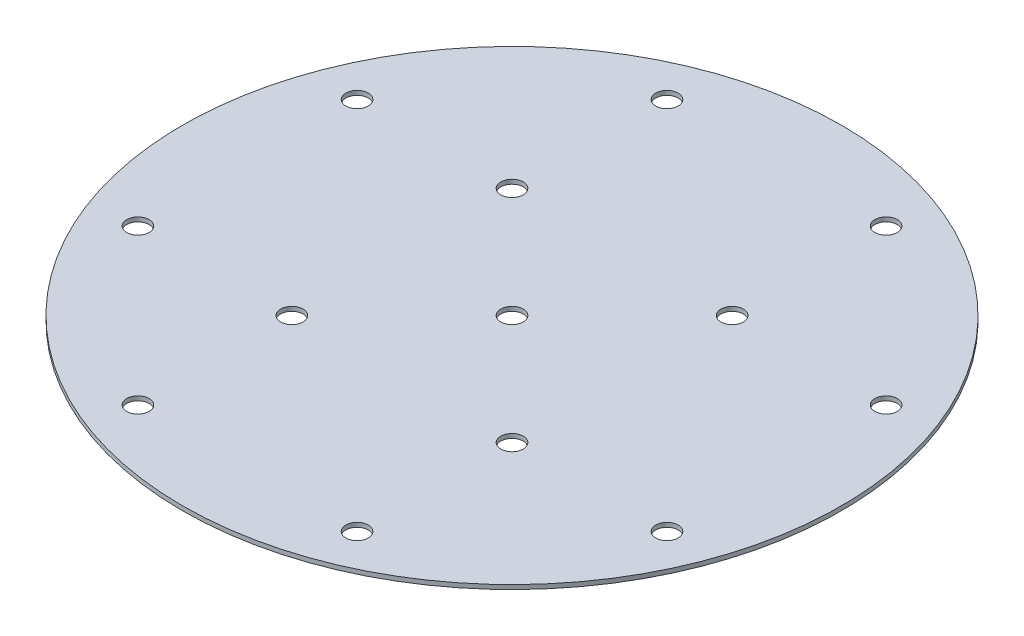
SolidWorks part; units mm, degrees
ref_plane "Front Plane" through (0, 0, 0) normal (0, 0, 1) x (1, 0, 0)
ref_plane "Top Plane" through (0, 0, 0) normal (0, 1, 0) x (1, 0, 0)
ref_plane "Right Plane" through (0, 0, 0) normal (1, 0, 0) x (0, 0, -1)
sketch "Sketch2" plane through (0, 0, 0) normal (1, 0, 0) x (0, 0, -1)
  line L0 (0, 0) -> (-76.2, 0)
  line L1 (-76.2, 0) -> (-76.2, 1)
  line L2 (-76.2, 1) -> (0, 1)
  line L5 (0, 1) -> (0, 0)
  dimension "D1" = 76.2
  dimension "D2" = 1
ref_axis "Axis1" through (0, -0.05, 0) along (0, 1, 0)
revolve "Revolve1" add sketch "Sketch2" angle 360 about axis through (0, -0.05, 0) along (0, 1, 0)
hole_wizard "#6 (0.204) Diameter Hole1" positions "Sketch6" profile "Sketch7" hole size "#6" standard "ANSI Inch" end condition through all
sketch "Sketch6" plane through (0, 1, 0) normal (0, 1, 0) x (1, 0, 0)
  line L0 (0, 0) -> (-53.438, 129.0108) construction
  line L2 (0, 0) -> (0, 109.0908) construction
  line L3 (0, 0) -> (-70.3996, 29.1605) construction
  line L4 (0, 0) -> (-47.7784, 47.7784) construction
  circle A0 centre (0, 0) radius 76.2 construction
  point P0 (-25.3336, 61.1608)
  point P11 (264.7437, 73.7878)
  point P20 (-61.1608, 25.3336)
  point P22 (-25.4558, 25.4558)
  dimension "D1" = 22.5
  dimension "D2" = 66.2
  dimension "D3" = 66.2
  dimension "D4" = 45
  dimension "D6" = 22.5
  dimension "D5" = 36
sketch "Sketch7" plane through (-25.3336, 1, -61.1608) normal (1, 0, 0) x (0, 0, 1)
  line L0 (0, 0) -> (0, 1)
  line L1 (0, 1) -> (2.5908, 1)
  line L2 (2.5908, 1) -> (2.5908, 0)
  line L5 (2.5908, 0) -> (0, 0)
  line L11 (0, -6.35) -> (0, 107.95) construction
  dimension "Thru Hole Dia." = 5.1816
  dimension "Thru Hole Depth" = 1
pattern_circular "CirPattern3" count 4 over 360 about axis through (0, -0.05, 0) along (0, 1, 0) of "#6 (0.204) Diameter Hole1"
hole_wizard "#6 (0.204) Diameter Hole2" positions "Sketch8" profile "Sketch9" hole size "#6" standard "ANSI Inch" end condition through all
sketch "Sketch8" plane through (0, 1, 0) normal (0, 1, 0) x (1, 0, 0)
  line L0 (0, 0) -> (106.3094, -1.7118) construction
  point P7 (0, 0)
sketch "Sketch9" plane through (0, 1, 0) normal (1, 0, 0) x (0, 0, 1)
  line L0 (0, 0) -> (0, 1)
  line L1 (0, 1) -> (2.5908, 1)
  line L2 (2.5908, 1) -> (2.5908, 0)
  line L5 (2.5908, 0) -> (0, 0)
  line L11 (0, -6.35) -> (0, 107.95) construction
  dimension "Thru Hole Dia." = 5.1816
  dimension "Thru Hole Depth" = 1
equation "\"TubeDiameter\" = 6.000in"
equation "\"D1@Sketch2\"=\"TubeDiameter\"/2"
equation "\"D2@Sketch6\"=\"TubeDiameter\"/2-10mm"
